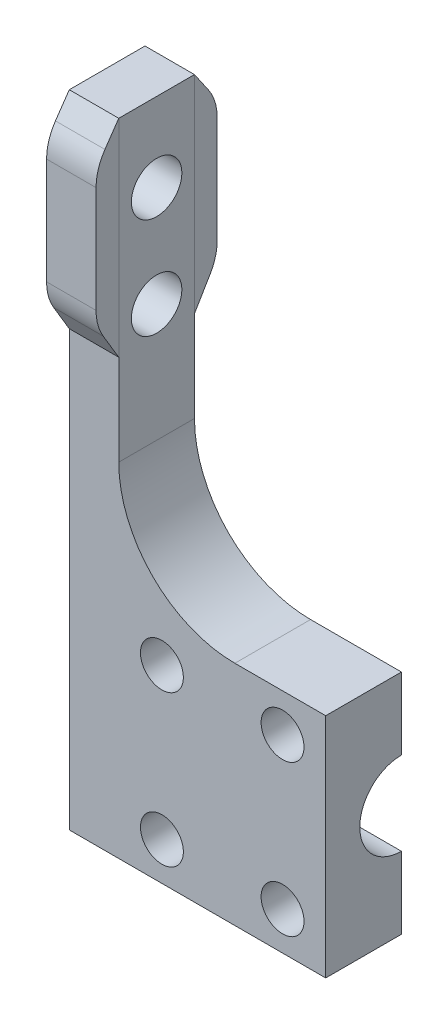
SolidWorks part; units mm, degrees
ref_plane "Front Plane" through (0, 0, 0) normal (0, 0, 1) x (1, 0, 0)
ref_plane "Top Plane" through (0, 0, 0) normal (0, 1, 0) x (1, 0, 0)
ref_plane "Right Plane" through (0, 0, 0) normal (1, 0, 0) x (0, 0, -1)
sketch "Sketch4" plane through (0, 0, 0) normal (0, 0, 1) x (1, 0, 0)
  line L0 (0, 0) -> (-11.95, -14.95) construction
  line L1 (-20.5, 22.5) -> (20.5, 22.5)
  line L2 (-20.5, 22.5) -> (-20.5, -22.5)
  line L3 (-20.5, -22.5) -> (20.5, -22.5)
  line L4 (20.5, 22.5) -> (20.5, -22.5)
  line L5 (0, 0) -> (11.95, -14.95) construction
  line L6 (0, 0) -> (11.95, 14.95) construction
  line L7 (-11.95, 14.95) -> (11.95, 14.95) construction
  line L8 (-11.95, 14.95) -> (-11.95, -14.95) construction
  line L9 (-11.95, -14.95) -> (11.95, -14.95) construction
  line L10 (11.95, 14.95) -> (11.95, -14.95) construction
  circle A4 centre (-11.95, 14.95) radius 4.25
  circle A5 centre (11.95, 14.95) radius 4.25
  circle A6 centre (11.95, -14.95) radius 4.25
  circle A7 centre (-11.95, -14.95) radius 4.25
  point P0 (0, 0)
  point P6 (0, 0)
  dimension "D3" = 8.5
  dimension "D4" = 23.9
  dimension "D1" = 41
  dimension "D2" = 45
  dimension "D5" = 29.9
extrude "Boss-Extrude1" add sketch "Sketch4" along normal blind 15
sketch "Sketch6" plane through (0, 0, 0) normal (0, 0, -1) x (-1, 0, 0)
  line L2 (20.5, -22.5) -> (20.5, 104.5)
  line L3 (20.5, 104.5) -> (30.3, 104.5)
  line L4 (30.3, 104.5) -> (30.3, -22.5)
  line L5 (30.3, -22.5) -> (20.5, -22.5)
  line L6 (-20.5, -22.5) -> (-20.5, 22.5) construction
  dimension "D1" = 50.8
  dimension "D2" = 127
extrude "Boss-Extrude2" add sketch "Sketch6" against normal blind 15
sketch "Sketch7" plane through (-20.5, 0, 0) normal (1, 0, 0) x (0, 0, -1)
  line L0 (-7.5, 104.5) -> (-7.5, 22.5) construction
  line L1 (-15, 104.5) -> (0, 104.5) construction
  line L2 (-15, 22.5) -> (0, 22.5) construction
  line L3 (0, 63.5) -> (3.0838, 68.66)
  line L5 (0, 104.5) -> (0, 22.5) construction
  line L6 (4.5, 73.7901) -> (4.5, 94.8519)
  line L7 (2.7383, 100.5202) -> (0, 104.5)
  line L8 (0, 63.5) -> (0, 104.5)
  line L9 (-15, 63.5) -> (-18.0838, 68.66)
  line L10 (-19.5, 73.7901) -> (-19.5, 94.8519)
  line L11 (-17.7383, 100.5202) -> (-15, 104.5)
  line L12 (-15, 63.5) -> (-15, 104.5)
  circle A0 centre (-7.5, 88.8749) radius 5
  circle A1 centre (-7.5, 68.8749) radius 5
  arc A2 (-18.0838, 68.66) -> (-19.5, 73.7901) centre (-9.5, 73.7901) cw
  arc A3 (3.0838, 68.66) -> (4.5, 73.7901) centre (-5.5, 73.7901) ccw
  arc A4 (4.5, 94.8519) -> (2.7383, 100.5202) centre (-5.5, 94.8519) ccw
  arc A5 (-19.5, 94.8519) -> (-17.7383, 100.5202) centre (-9.5, 94.8519) cw
  point P23 (-19.5, 71.0296)
  point P26 (4.5, 71.0296)
  point P29 (4.5, 97.9598)
  point P32 (-19.5, 97.9598)
  dimension "D1" = 20
  dimension "D2" = 10
  dimension "D4" = 10
  dimension "D3" = 12
extrude "Boss-Extrude3" add sketch "Sketch7" along direction (-1, 0, 0) on the side against the normal up to surface (9.8 mm away) up to face at (-30.3, 41, 7.5)
sketch "Sketch8" plane through (-20.5, 0, 0) normal (1, 0, 0) x (0, 0, -1)
  circle A1 centre (-7.5, 68.8749) radius 5
  circle A2 centre (-7.5, 68.8749) radius 5
  circle A3 centre (-7.5, 88.8749) radius 5
  circle A4 centre (-7.5, 88.8749) radius 5
  dimension "D1" = 0
  dimension "D2" = 0
extrude "Cut-Extrude2" cut sketch "Sketch8" against normal blind 15
sketch "Sketch5" plane through (20.5, 0, 0) normal (1, 0, 0) x (0, 0, -1)
  line L0 (0, -22.5) -> (0, 22.5) construction
  circle A0 centre (0, 0) radius 8.25
  dimension "D1" = 16.5
extrude "Cut-Extrude1" cut sketch "Sketch5" against normal blind 65
sketch "Sketch9" plane through (0, 0, 0) normal (0, 0, -1) x (-1, 0, 0)
  line L4 (-2.5, 22.5) -> (20.5, 22.5)
  line L5 (20.5, 22.5) -> (20.5, 45.5)
  arc A0 (-2.5, 22.5) -> (20.5, 45.5) centre (-2.5, 45.5) ccw
  point P9 (20.5, 22.5)
  dimension "D1" = 23
extrude "Boss-Extrude4" add sketch "Sketch9" against normal blind 15
ref_axis "Axis1" through (-30.3, 0, 0) along (1, 0, 0)
